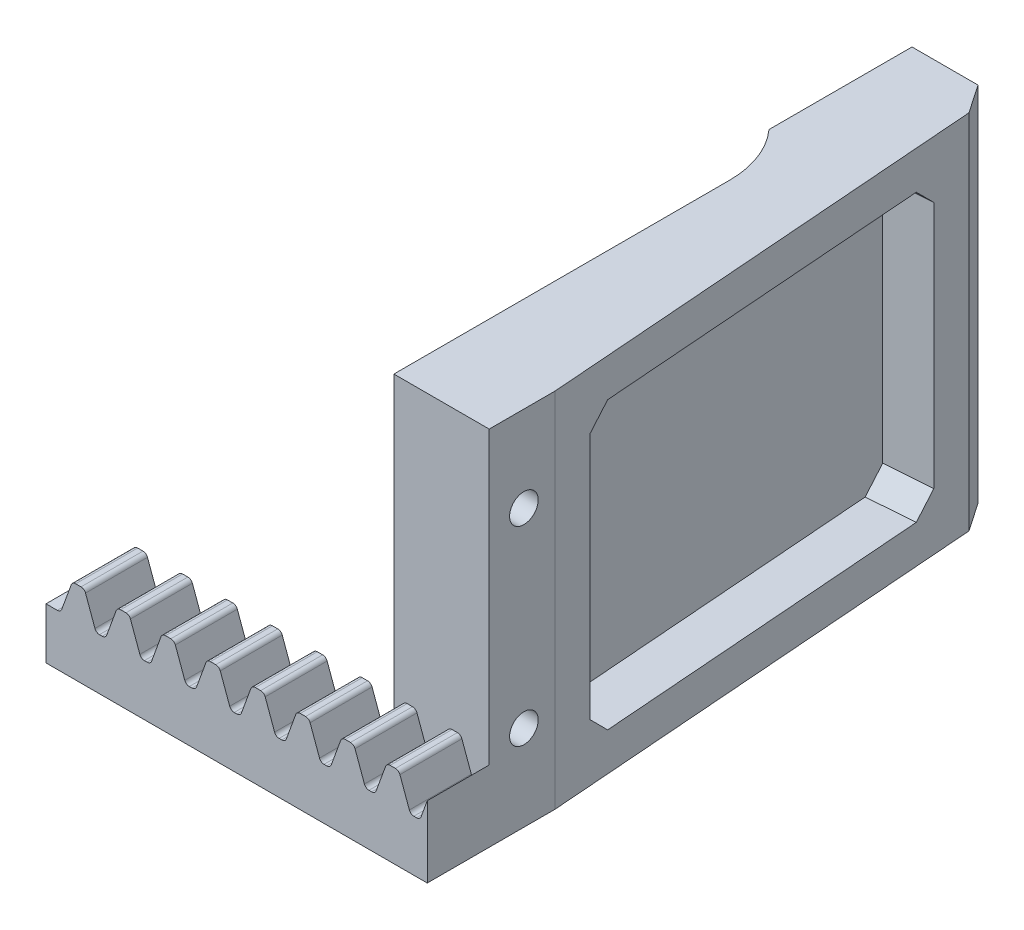
SolidWorks part; units mm, degrees
ref_plane "Front Plane" through (0, 0, 0) normal (0, 0, 1) x (1, 0, 0)
ref_plane "Top Plane" through (0, 0, 0) normal (0, 1, 0) x (1, 0, 0)
ref_plane "Right Plane" through (0, 0, 0) normal (1, 0, 0) x (0, 0, -1)
sketch "Sketch1" plane through (0, 0, 0) normal (0, 0, 1) x (1, 0, 0)
  line L0 (-100, 7.5) -> (-100, -7.5) construction
  line L1 (-100, -7.5) -> (100, -7.5) construction
  line L2 (100, -7.5) -> (100, 7.5) construction
  line L4 (0, 7.5) -> (0, -7.5) construction
  line L5 (-100, 6) -> (100, 6) construction
  line L6 (-97.2361, 7.5) -> (-95.9718, 7.5) construction
  line L7 (-95.9718, 7.5) -> (-94.7434, 4.125) construction
  line L8 (-97.2361, 7.5) -> (-98.4645, 4.125) construction
  line L9 (-98.4645, 4.125) -> (-94.7434, 4.125) construction
  line L10 (-96.604, 7.5) -> (-96.604, 4.125) construction
  line L11 (-100, 0) -> (-87.1792, 0) construction
  line L12 (100, 0) -> (87.1792, 0) construction
  point P15 (-91.8916, 7.5)
  point P16 (-21, -7.5)
  point P17 (-95.4259, 6)
  point P18 (-97.7821, 6)
  point P21 (-0.75, -7.5)
  dimension "Length" = 200
  dimension "Height" = 15
  dimension "Number of Teeth" = 42
  dimension "Pressure Angle" = 20
  dimension "Circular Pitch" = 4.7124
  dimension "Addendum" = 1.5
  dimension "Dedendum" = 1.875
  dimension "Circular Tooth Thickness" = 2.3562
  dimension "Rack Length" = 193.2079
  dimension "D1" = 9.4248
  dimension "For Module" = 1.5
sketch "Sketch2" plane through (0, 0, 0) normal (1, 0, 0) x (0, 0, -1)
  line L0 (-7.5, 0) -> (7.5, 0) construction
  dimension "Face Width" = 15
sketch "Sketch3" plane through (0, 0, 0) normal (0, 0, 1) x (1, 0, 0)
  line L1 (-100, 7.5) -> (100, 7.5)
  line L2 (-100, 7.5) -> (-100, -7.5)
  line L3 (-100, -7.5) -> (100, -7.5)
  line L4 (100, 7.5) -> (100, -7.5)
extrude "Boss-Extrude1" add sketch "Sketch3" against normal up to vertex (7.5 mm away) and the other way up to vertex (7.5 mm away) up to point (0, 0, -7.5) other way up to point (0, 0, 7.5)
sketch "Sketch4" plane through (0, 0, 0) normal (0, 0, 1) x (1, 0, 0)
  line L0 (-96.604, 7.5) -> (-91.8916, 7.5) construction
  line L9 (-94.2478, 7.5) -> (-94.2478, 4.125)
  line L10 (-94.2478, 4.125) -> (-94.7434, 4.125)
  line L11 (-94.7434, 4.125) -> (-95.9718, 7.5)
  line L12 (-95.9718, 7.5) -> (-94.2478, 7.5)
  line L13 (-97.2361, 7.5) -> (-98.4645, 4.125)
  line L14 (-98.4645, 4.125) -> (-98.9602, 4.125)
  line L15 (-98.9602, 4.125) -> (-98.9602, 7.5)
  line L16 (-98.9602, 7.5) -> (-97.2361, 7.5)
extrude "Cut-Extrude1" cut sketch "Sketch4" against normal through all both and the other way through all
fillet "Fillet1" radius 0.5033 4 edges at (-98.4645, 4.125, 0) (-94.7434, 4.125, 0) (-95.9718, 7.5, 0) (-97.2361, 7.5, 0)
pattern_linear "LPattern1" count 42 spacing 4.7124 along (1, 0, 0) of "Cut-Extrude1", "Fillet1"
sketch "Sketch5" plane through (0, 0, 0) normal (0, 0, 1) x (1, 0, 0)
  line L0 (-100, 6) -> (-103.6726, 6) construction
  line L1 (-98.9602, 4.125) -> (-103.6726, 4.125)
  line L2 (-98.9602, 4.125) -> (-98.9602, 7.5)
  line L3 (-98.9602, 7.5) -> (-103.6726, 7.5)
  line L4 (-103.6726, 4.125) -> (-103.6726, 7.5)
  line L5 (98.9602, 7.5) -> (103.6726, 7.5)
  line L6 (98.9602, 7.5) -> (98.9602, 4.125)
  line L7 (98.9602, 4.125) -> (103.6726, 4.125)
  line L8 (103.6726, 7.5) -> (103.6726, 4.125)
  line L9 (103.6726, 6) -> (100, 6) construction
  dimension "D1" = 4.7124
extrude "Cut-Extrude2" cut sketch "Sketch5" against normal through all both and the other way through all
sketch "Sketch6" plane through (0, 0, 0) normal (1, 0, 0) x (0, 0, -1)
  line L0 (-7.5, -7.5) -> (-7.5, 4.125) construction
  line L1 (-1, 10.225) -> (12.8906, 10.225)
  line L2 (-1, 10.225) -> (-1, -11.7256)
  line L3 (-1, -11.7256) -> (12.8906, -11.7256)
  line L4 (12.8906, 10.225) -> (12.8906, -11.7256)
  dimension "D1" = 6.5
extrude "Cut-Extrude3" cut sketch "Sketch6" against normal through all both and the other way through all
sketch "Sketch8" plane through (0, 0, 0) normal (0, 0, 1) x (1, 0, 0)
  line L0 (-100, 4.125) -> (-100, -7.5) construction
  line L1 (-60, 29.716) -> (115.1008, 29.716)
  line L2 (-60, 29.716) -> (-60, -15.2308)
  line L3 (-60, -15.2308) -> (115.1008, -15.2308)
  line L4 (115.1008, 29.716) -> (115.1008, -15.2308)
  dimension "D1" = 40
extrude "Cut-Extrude6" cut sketch "Sketch8" against normal through all and the other way through all
sketch "Sketch9" plane through (0, 0, 0) normal (0, 0, 1) x (1, 0, 0)
  line L0 (-86.8994, 7.5) -> (-87.459, 7.5) construction
  line L1 (-104.5799, -1.25) -> (-49.0781, -1.25)
  line L2 (-104.5799, -1.25) -> (-104.5799, -12.034)
  line L3 (-104.5799, -12.034) -> (-49.0781, -12.034)
  line L4 (-49.0781, -1.25) -> (-49.0781, -12.034)
  dimension "D1" = 8.75
extrude "Cut-Extrude7" cut sketch "Sketch9" along normal through all
sketch "Sketch10" plane through (0, 0, 1) normal (0, 0, -1) x (-1, 0, 0)
  line L1 (60, -1.25) -> (70, -1.25)
  line L2 (60, -1.25) -> (60, 36.75)
  line L3 (60, 36.75) -> (70, 36.75)
  line L4 (70, -1.25) -> (70, 36.75)
  dimension "D1" = 38
  dimension "D2" = 10
extrude "Boss-Extrude2" add sketch "Sketch10" along normal blind 6.9
sketch "Sketch11" plane through (0, 0, -5.9) normal (0, 0, -1) x (-1, 0, 0)
  line L0 (100, -1.25) -> (70, -1.25) construction
  line L1 (60, 36.75) -> (72.54, 36.75)
  line L2 (60, 36.75) -> (60, -1.25)
  line L3 (60, -1.25) -> (72.54, -1.25)
  line L4 (72.54, 36.75) -> (72.54, -1.25)
  dimension "D1" = 12.54
extrude "Boss-Extrude3" add sketch "Sketch11" along normal blind 50
sketch "Sketch12" plane through (0, -1.25, 0) normal (0, -1, 0) x (1, 0, 0)
  line L0 (-60, -55.9) -> (-72.54, -55.9) construction
  line L1 (-72.54, -5.9) -> (-70, -5.9)
  line L2 (-72.54, -5.9) -> (-72.54, -40.9)
  line L3 (-72.54, -40.9) -> (-70, -40.9)
  line L4 (-70, -5.9) -> (-70, -40.9)
  line L5 (-70, -5.9) -> (-70, 1) construction
  line L6 (-60, -5.9) -> (-63.8, -55.9)
  line L7 (-60, 7.5) -> (-60, -55.9) construction
  line L8 (-63.8, -55.9) -> (-60, -55.9)
  line L9 (-60, -55.9) -> (-60, -5.9)
  dimension "D1" = 15
  dimension "D2" = 3.8
extrude "Cut-Extrude8" cut sketch "Sketch12" against normal through all
chamfer "Chamfer1" distance 3 angle 30 1 edges at (-63.8, 17.75, -55.9) first distance on face at (-61.9, 17.75, -30.9)
fillet "Fillet2" radius 10 1 edges at (-70, 17.75, -40.9)
sketch "Sketch13" plane through (-59.2096, 0, 4.4999) normal (0.9971, 0, -0.0758) x (-0.0758, 0, -0.9971)
  line L8 (14.4299, 2.75) -> (53.5741, 2.75)
  line L9 (53.5741, 2.75) -> (53.5741, 32.75)
  line L10 (53.5741, 32.75) -> (14.4299, 32.75)
  line L11 (14.4299, 32.75) -> (14.4299, 2.75)
  line L12 (14.4299, 2.75) -> (53.5741, 2.75)
  line L13 (53.5741, 2.75) -> (53.5741, 32.75)
  line L14 (53.5741, 32.75) -> (14.4299, 32.75)
  line L15 (14.4299, 32.75) -> (14.4299, 2.75)
  dimension "D1" = 4
extrude "Cut-Extrude9" cut sketch "Sketch13" against normal blind 5
chamfer "Chamfer2" distance 2 angle 45 4 edges at (-62.7959, 2.75, -9.699) (-65.7623, 2.75, -48.7307) (-65.7623, 32.75, -48.7307) (-62.7959, 32.75, -9.699)
sketch "Sketch14" plane through (-60, 0, 0) normal (1, 0, 0) x (0, 0, -1)
  line L0 (5.9, 36.75) -> (5.9, -1.25) construction
  line L1 (5.9, 36.75) -> (-1, 36.75) construction
  line L2 (-7.5, -1.25) -> (5.9, -1.25) construction
  circle A0 centre (2.64, 27.75) radius 1.5
  circle A1 centre (2.64, 7.75) radius 1.5
  dimension "D1" = 3
  dimension "D2" = 3.26
  dimension "D3" = 9
  dimension "D4" = 9
  dimension "D5" = 3.26
extrude "Cut-Extrude10" cut sketch "Sketch14" against normal through all
equation "\"Diametral Pitch\"= 1 / \"Module\""
equation "\"Pressure Angle\"=20"
equation "\"Dedendum\"= 1.25 / \"Diametral Pitch\""
equation "\"Addendum\"= 1 / \"Diametral Pitch\""
equation "\"WorkingDepth\"= 2 / \"Diametral Pitch\""
equation "\"WholeDepth\"= 2.25 / \"Diametral Pitch\""
equation "\"Clearance\"= 0.25 / \"Diametral Pitch\""
equation "\"ToothThickness\"= ( pi / 2 ) / \"Diametral Pitch\""
equation "\"CircularPitch\"= pi / \"Diametral Pitch\""
equation "\"Fillet\"= \"Clearance\" * cos ( \"Pressure Angle\" ) * tan ( ( 90 + \"Pressure Angle\" ) / 2 )"
equation "\"Module\"= 1.5"
equation "\"Addendum@Sketch1\"=\"Addendum\""
equation "\"Pressure Angle@Sketch1\"=\"Pressure Angle\""
equation "\"Dedendum@Sketch1\"=\"Dedendum\""
equation "\"Circular Pitch@Sketch1\"=\"CircularPitch\""
equation "\"Circular Tooth Thickness@Sketch1\"=\"ToothThickness\""
equation "\"Number of Teeth@Sketch1\"=int(\"Length@Sketch1\"/(2*\"Circular Tooth Thickness@Sketch1\"))"
equation "\"Rack Length@Sketch1\"=\"Circular Pitch@Sketch1\"*(\"Number of Teeth@Sketch1\"-1)"
equation "\"D3@LPattern1\"=\"CircularPitch\""
equation "\"D1@LPattern1\"=\"Number of Teeth@Sketch1\""
equation "\"D1@Sketch1\"=\"Circular Pitch@Sketch1\"*2"
equation "\"D1@Fillet1\"=\"Fillet\""
equation "\"For Module@Sketch1\"=\"Module\""
equation "\"D4@LPattern1\"=\"CircularPitch\""
equation "\"D1@Sketch5\"=\"CircularPitch\""
